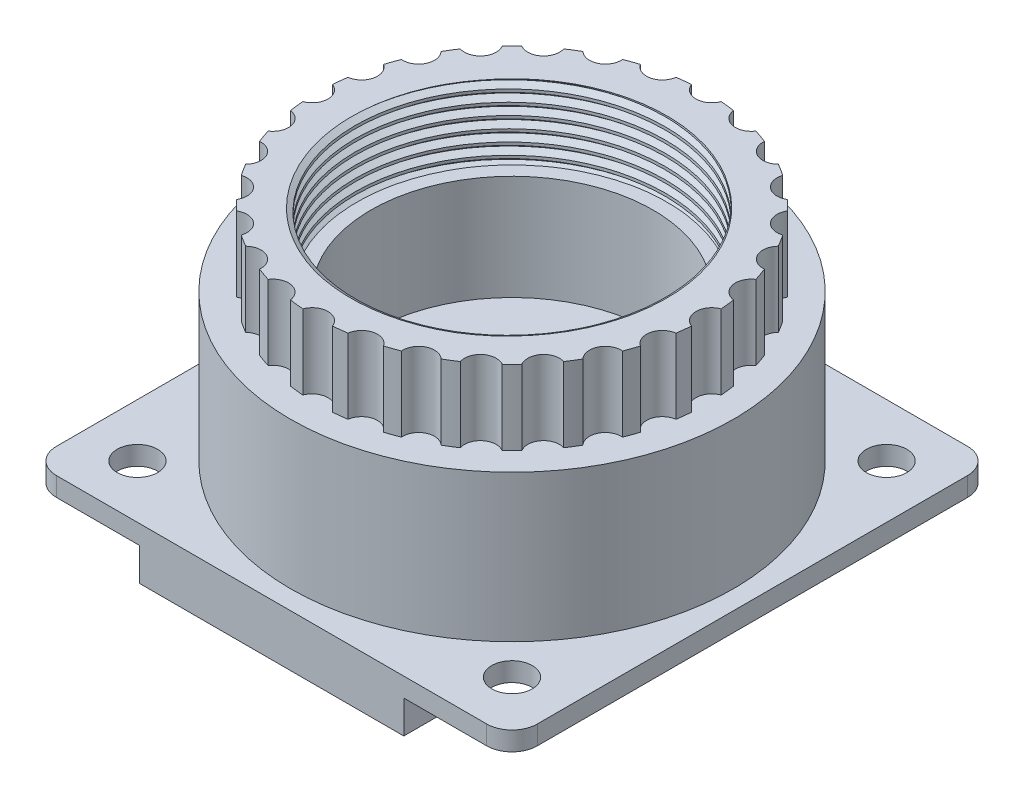
SolidWorks part; units mm, degrees
ref_plane "Front Plane" through (0, 0, 0) normal (0, 0, 1) x (1, 0, 0)
ref_plane "Top Plane" through (0, 0, 0) normal (0, 1, 0) x (1, 0, 0)
ref_plane "Right Plane" through (0, 0, 0) normal (1, 0, 0) x (0, 0, -1)
sketch "Sketch1" plane through (0, 0, 0) normal (0, 1, 0) x (1, 0, 0)
  line L0 (-14.8, 16.4) -> (-14.8, 19) construction
  line L1 (-19, -19) -> (19, -19)
  line L2 (-19, -19) -> (-19, 19)
  line L3 (-19, 19) -> (19, 19)
  line L4 (19, -19) -> (19, 19)
  line L5 (-19, -19) -> (19, 19) construction
  line L6 (-19, 19) -> (19, -19) construction
  line L12 (14.8, -14.8) -> (-14.8, -14.8) construction
  line L13 (14.8, -14.8) -> (14.8, 14.8) construction
  line L14 (14.8, 14.8) -> (-14.8, 14.8) construction
  line L15 (-14.8, -14.8) -> (-14.8, 14.8) construction
  line L16 (14.8, -14.8) -> (-14.8, 14.8) construction
  line L17 (14.8, 14.8) -> (-14.8, -14.8) construction
  circle A0 centre (-14.8, 14.8) radius 1.6
  circle A1 centre (-14.8, -14.8) radius 1.6
  circle A2 centre (14.8, -14.8) radius 1.6
  circle A3 centre (14.8, 14.8) radius 1.6
  point P0 (0, 0)
  point P10 (0, 0)
  dimension "D3" = 3.2
  dimension "D1" = 38
  dimension "D2" = 38
  dimension "D4" = 2.6
extrude "Boss-Extrude1" add sketch "Sketch1" along normal mid plane 1.5
sketch "Sketch2" plane through (0, -0.75, 0) normal (0, -1, 0) x (1, 0, 0)
  line L0 (-19, 19) -> (19, 19) construction
  line L1 (10.45, 13.3) -> (-10.45, 13.3)
  line L2 (10.45, 13.3) -> (10.45, 19)
  line L3 (10.45, 19) -> (-10.45, 19)
  line L4 (-10.45, 13.3) -> (-10.45, 19)
  line L5 (10.45, 13.3) -> (-10.45, 19) construction
  line L6 (10.45, 19) -> (-10.45, 13.3) construction
  point P0 (0, 16.15)
  dimension "D1" = 20.9
  dimension "D2" = 5.7
extrude "Boss-Extrude2" add sketch "Sketch2" along normal blind 2.6
sketch "Sketch13" plane through (0, 0.75, 0) normal (0, 1, 0) x (1, 0, 0)
  line L1 (3.625, -2.25) -> (-3.625, -2.25)
  line L2 (3.625, -2.25) -> (3.625, 2.25)
  line L3 (3.625, 2.25) -> (-3.625, 2.25)
  line L4 (-3.625, -2.25) -> (-3.625, 2.25)
  line L5 (3.625, -2.25) -> (-3.625, 2.25) construction
  line L6 (3.625, 2.25) -> (-3.625, -2.25) construction
  point P0 (0, 0)
  dimension "D1" = 4.5
  dimension "D2" = 7.25
extrude "Boss-Extrude8" add sketch "Sketch13" along normal blind 0.25
sketch "Sketch3" plane through (0, -0.75, 0) normal (0, -1, 0) x (1, 0, 0)
  line L0 (12.125, 0) -> (-12.125, 0) construction
  line L1 (-13.9, 0) -> (13.9, 0) construction
  circle A0 centre (-12.125, 0) radius 1.775
  circle A1 centre (12.125, 0) radius 1.775
  point P8 (0, 0)
  dimension "D1" = 3.55
  dimension "D2" = 27.8
extrude "Boss-Extrude3" add sketch "Sketch3" along normal blind 3.25 separate body
sketch "Sketch4" plane through (0, 0.75, 0) normal (0, 1, 0) x (1, 0, 0)
  circle A0 centre (0, 0) radius 17.5
  circle A1 centre (0, 0) radius 11.15
  dimension "D1" = 35
  dimension "D2" = 22.3
extrude "Boss-Extrude4" add sketch "Sketch4" along normal blind 11.6 separate body
sketch "Sketch14" plane through (0, 0.75, 0) normal (0, 1, 0) x (1, 0, 0)
  circle A0 centre (-12.125, 0) radius 1.775 construction
  circle A1 centre (12.125, 0) radius 1.775 construction
  circle A2 centre (-12.125, 0) radius 1.775 construction
  circle A3 centre (12.125, 0) radius 1.775 construction
  circle A4 centre (-12.125, 0) radius 0.7
  circle A5 centre (12.125, 0) radius 0.7
  dimension "D1" = 1.4
extrude "Cut-Extrude2" cut sketch "Sketch14" against normal up to surface (1.5 mm away) and the other way blind 5 up to face at (0, -0.75, 8.075)
sketch "Sketch5" plane through (0, 12.35, 0) normal (0, 1, 0) x (1, 0, 0)
  circle A0 centre (0, 0) radius 15.4
  circle A1 centre (0, 0) radius 12.24
  dimension "D1" = 30.8
  dimension "D2" = 3.16
extrude "Boss-Extrude5" add sketch "Sketch5" along normal blind 5.9
thread "Thread1" pitch 0.9071 method cut profile "Thread Profile1" start angle 0, offset 1, length 0, pitch 0.9071, diameter 24.48
ref_plane "Plane1" through (-12.24, 19.25, 0) normal (0, 0, 1) x (-1, 0, 0)
sketch "Thread Profile1" plane through (-12.24, 19.25, 0) normal (0, 0, 1) x (-1, 0, 0)
  line L0 (0, 0) -> (0, 0.9071) construction
  line L1 (0, 0) -> (0.491, 0.2835)
  line L2 (0.491, 0.2835) -> (0.491, 0.3969)
  line L3 (0.491, 0.3969) -> (0, 0.6804)
  line L4 (0.491, 0.3402) -> (0, 0.3402) construction
  line L11 (0, 0) -> (0, 0.6804)
  point P2 (0, 0)
  dimension "Pitch" = 0.9071
  dimension "Profile_Angle" = 60
  dimension "Profile_Land" = 0.1134
  dimension "Profile_Height" = 0.491
sketch "Sketch10" plane through (0, 18.25, 0) normal (0, 1, 0) x (1, 0, 0)
  line L0 (0, 15.79) -> (0, 0) construction
  line L1 (0, 14.54) -> (0, 12.24) construction
  circle A0 centre (0, 15.79) radius 1.25
  arc A1 (7.3024, 9.823) -> (-9.823, 7.3024) centre (0, 0) ccw construction
  dimension "D1" = 2.5
  dimension "D2" = 2.3
extrude "Cut-Extrude1" cut sketch "Sketch10" against normal up to surface (5.9 mm away) up to face at (0, 12.35, 11.15)
pattern_circular "CirPattern1" count 28 over 360 about axis through (0, 18.25, 0) along (0, 1, 0) of "Cut-Extrude1"
sketch "Sketch11" plane through (0, 0.75, 0) normal (0, 1, 0) x (1, 0, 0)
  line L1 (4.5, -4) -> (-4.5, -4)
  line L2 (4.5, -4) -> (4.5, 4)
  line L3 (4.5, 4) -> (-4.5, 4)
  line L4 (-4.5, -4) -> (-4.5, 4)
  line L5 (4.5, -4) -> (-4.5, 4) construction
  line L6 (4.5, 4) -> (-4.5, -4) construction
  circle A0 centre (0, 0) radius 11.15 construction
  circle A1 centre (0, 0) radius 11.15
  point P8 (0, 0)
  dimension "D2" = 8
  dimension "D3" = 9
extrude "Boss-Extrude6" add sketch "Sketch11" along normal offset from surface (3.3 mm away) 14.2 up to face at (0, 18.25, 0)
sketch "Sketch15" plane through (0, -0.75, 0) normal (0, 1, 0) x (1, 0, 0)
  circle A0 centre (12.125, 0) radius 1.775 construction
  circle A1 centre (-12.125, 0) radius 1.775 construction
  circle A2 centre (12.125, 0) radius 1.775 construction
  circle A3 centre (-12.125, 0) radius 1.775 construction
  circle A4 centre (-12.125, 0) radius 0.7
  circle A5 centre (12.125, 0) radius 0.7
  circle A6 centre (-12.125, 0) radius 0.7 construction
extrude "Boss-Extrude9" add sketch "Sketch15" along normal blind 6
delete or keep bodies "Body-Delete/Keep 1" [suppressed] type delete bodies bodies 116 109 115
fillet "Fillet1" radius 2 4 edges at (-19, 0, -19) (19, 0, -19) (19, 0, 19) (-19, 0, 19)
